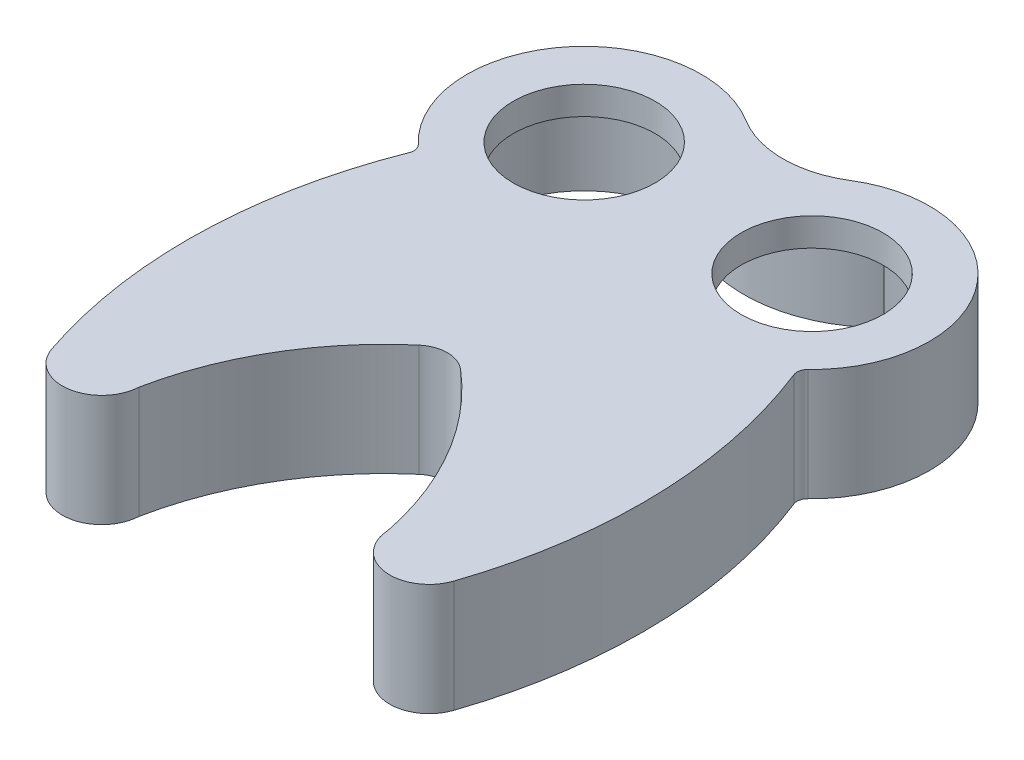
SolidWorks part; units mm, degrees
ref_plane "Přední rovina" through (0, 0, 0) normal (0, 0, 1) x (1, 0, 0)
ref_plane "Horní rovina" through (0, 0, 0) normal (0, 1, 0) x (1, 0, 0)
ref_plane "Pravá rovina" through (0, 0, 0) normal (1, 0, 0) x (0, 0, -1)
sketch "Skica3" plane through (0, 0, 0) normal (0, 1, 0) x (1, 0, 0)
  line L0 (0, 32.0454) -> (0, -53.7479) construction
  arc A0 (-6.1081, 20.1548) -> (-20.2003, 1.9375) centre (-12.2116, 10.317) ccw
  arc A2 (-20.6006, -37.0887) -> (-14.3184, -36.1513) centre (-17.5436, -36.0563) ccw
  arc A5 (2.8834, -16.6205) -> (-2.8834, -16.6205) centre (0, -20) ccw
  arc A6 (-6.1081, 20.1548) -> (6.1081, 20.1548) centre (0, 30) ccw
  arc A8 (-2.8834, -16.6205) -> (-14.4933, -37.1084) centre (19.4718, -42.8221) ccw
  arc A9 (-19.6841, -0.4058) -> (-20.6006, -37.0887) centre (30, -20) ccw
  arc A10 (-19.6841, -0.4058) -> (-20.2003, 1.9375) centre (-21.6828, 0.3824) ccw
  arc A12 (6.1081, 20.1548) -> (20.2003, 1.9375) centre (12.2116, 10.317) cw
  arc A13 (19.6841, -0.4058) -> (20.2003, 1.9375) centre (21.6828, 0.3824) cw
  arc A14 (19.6841, -0.4058) -> (20.6006, -37.0887) centre (-30, -20) cw
  arc A15 (20.6006, -37.0887) -> (14.3184, -36.1513) centre (17.5436, -36.0563) cw
  arc A16 (2.8834, -16.6205) -> (14.4933, -37.1084) centre (-19.4718, -42.8221) cw
  arc A17 (-9.6515, 20.1548) -> (9.857, 20.3605) centre (0, 30) ccw
  arc A18 (-14.3184, -0.4058) -> (13.8424, -1.0431) centre (0.1454, 16.2138) ccw
extrude "Vysunout tenkostěnný1" add sketch "Skica3" against normal blind 9 thin contours A15 A14 A13 A12 A6 A0 A10 A9 A2 | A16 A5 A8 thin type mid plane wall 2
extrude "Vysunout tenkostěnný2" add sketch "Skica3<3>" against normal blind 7.5 thin contours A18 | A17 thin type one direction wall 1
sketch "Skica3<3>" plane through (0, 0, 0) normal (0, 1, 0) x (1, 0, 0) same geometry as "Skica3"
extrude "Přidat vysunutím2" add sketch "Skica3<4>" along normal blind 3 contours L0 A6 A0 A10 A9 A2 A8 A5 | A6 L0 A5 A16 A15 A14 A13 A12 region at (12.3765, 0, 4.7162) region at (-12.3765, 0, 4.7162)
sketch "Skica3<4>" plane through (0, 0, 0) normal (0, 1, 0) x (1, 0, 0) same geometry as "Skica3"
extrude "Vysunout tenkostěnný3" add sketch "Skica3<5>" along normal blind 3 thin thin type mid plane wall 2
sketch "Skica3<5>" plane through (0, 0, 0) normal (0, 1, 0) x (1, 0, 0) same geometry as "Skica3"
sketch "Skica4" plane through (0, 0, 0) normal (0, 1, 0) x (1, 0, 0)
  circle A2 centre (-12.2116, 10.317) radius 7.5995
  arc A3 (-5.5809, 21.0045) -> (-20.8903, 1.2137) centre (-12.2116, 10.317) ccw construction
  circle A4 centre (12.2116, 10.317) radius 7.5995
  arc A5 (20.8903, 1.2137) -> (5.5809, 21.0045) centre (12.2116, 10.317) ccw construction
extrude "Odebrat vysunutím1" cut sketch "Skica4" along normal blind 10
